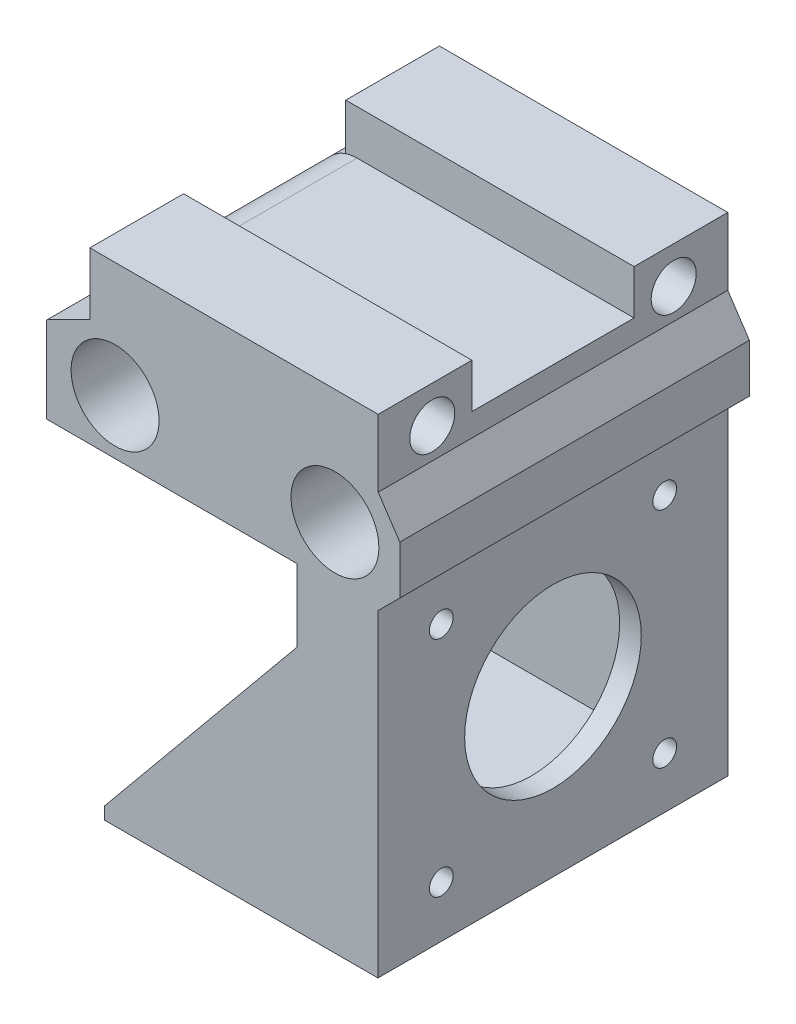
SolidWorks part; units mm, degrees
ref_plane "Front Plane" through (0, 0, 0) normal (0, 0, 1) x (1, 0, 0)
ref_plane "Top Plane" through (0, 0, 0) normal (0, 1, 0) x (1, 0, 0)
ref_plane "Right Plane" through (0, 0, 0) normal (1, 0, 0) x (0, 0, -1)
sketch "Sketch1" plane through (0, 0, 0) normal (0, 0, 1) x (1, 0, 0)
  line L0 (-37.9035, 31.8856) -> (4.5965, 31.8856)
  line L1 (-37.9035, 31.8856) -> (-37.9035, -23.9644)
  line L2 (-37.9035, -23.9644) -> (4.5965, -23.9644)
  line L3 (4.5965, -23.9644) -> (4.5965, 31.8856)
  dimension "D1" = 42.5
  dimension "D2" = 55.85
extrude "Boss-Extrude2" add sketch "Sketch1" along normal blind 42.5
sketch "Sketch5" plane through (0, 0, 42.5) normal (0, 0, 1) x (1, 0, 0)
  line L0 (-31.9035, 31.8856) -> (-31.9035, 20.046) construction
  line L1 (4.5965, 31.8856) -> (-37.9035, 31.8856) construction
  line L2 (-37.9035, 25.8856) -> (-26.7205, 25.8856) construction
  line L3 (-37.9035, 31.8856) -> (-37.9035, -23.9644) construction
  line L4 (-16.6535, 31.8856) -> (-16.6535, 20.4837) construction
  circle A0 centre (-31.9035, 25.9658) radius 3.175
  circle A1 centre (-1.4035, 25.9658) radius 3.175
  dimension "D3" = 6.35
  dimension "D1" = 6
  dimension "D2" = 6
extrude "Cut-Extrude2" cut sketch "Sketch5" against normal blind 42.5
sketch "Sketch6" plane through (-37.9035, 0, 0) normal (-1, 0, 0) x (0, 0, 1)
  line L0 (21.25, 22.7908) -> (21.25, -23.9644) construction
  line L1 (0, 22.7908) -> (42.5, 22.7908) construction
  line L2 (42.5, -23.9644) -> (0, -23.9644) construction
  line L3 (21.25, -0.5868) -> (0, -0.5868) construction
  line L4 (0, 31.8856) -> (0, -23.9644) construction
  line L5 (0, 20.6632) -> (42.5, 20.6632)
  line L6 (42.5, 31.8856) -> (42.5, -23.9644) construction
  line L7 (42.5, 20.6632) -> (42.5, -21.8368)
  line L8 (42.5, -21.8368) -> (0, -21.8368)
  line L9 (0, -21.8368) -> (0, 20.6632)
  dimension "D1" = 42.5
extrude "Cut-Extrude3" cut sketch "Sketch6" against normal blind 39.5
sketch "Sketch7" plane through (4.5965, 0, 0) normal (1, 0, 0) x (0, 0, -1)
  line L0 (-21.25, -21.8368) -> (-21.25, 20.6632) construction
  line L1 (0, -21.8368) -> (-42.5, -21.8368) construction
  line L2 (-42.5, 20.6632) -> (0, 20.6632) construction
  line L3 (-42.5, 20.6632) -> (0, 20.6632) construction
  line L4 (-42.5, -23.9644) -> (-42.5, 31.8856) construction
  line L5 (-42.5, -0.5868) -> (0, -0.5868) construction
  line L6 (0, 20.6632) -> (0, -21.8368) construction
  line L7 (0, -21.8368) -> (-42.5, -21.8368) construction
  line L8 (-42.5, -21.8368) -> (-42.5, 20.6632) construction
  line L9 (-42.5, -16.3368) -> (0, -16.3368) construction
  line L10 (-36.75, 20.6632) -> (-36.75, -21.8368) construction
  line L11 (-42.5, 14.6632) -> (0, 14.6632) construction
  circle A0 centre (-21.25, -0.5868) radius 12.25
  circle A1 centre (-36.75, -16.3368) radius 1.65
  circle A2 centre (-5.75, -16.3368) radius 1.65
  circle A3 centre (-36.75, 14.6632) radius 1.65
  circle A4 centre (-5.75, 14.6632) radius 1.65
  dimension "D1" = 5.5
  dimension "D3" = 31
  dimension "D5" = 31
  dimension "D6" = 3.3
  dimension "D7" = 3.3
  dimension "D8" = 24.5
  dimension "D2" = 31
  dimension "D4" = 6
extrude "Cut-Extrude4" cut sketch "Sketch7" against normal blind 39.5
sketch "Sketch9" plane through (0, -23.9644, 0) normal (0, -1, 0) x (1, 0, 0)
  line L0 (-37.9035, 42.5) -> (-27.9035, 42.5)
  line L1 (-37.9035, 42.5) -> (4.5965, 42.5) construction
  line L2 (-27.9035, 42.5) -> (-27.9035, 0)
  line L3 (-37.9035, 0) -> (4.5965, 0) construction
  line L4 (-27.9035, 0) -> (-37.9035, 0)
  line L5 (-37.9035, 0) -> (-37.9035, 42.5)
extrude "Cut-Extrude5" cut sketch "Sketch9" against normal blind 39.5
chamfer "Chamfer1" distance 3 angle 45 2 edges at (-37.9035, 31.8856, 21.25) (-37.9035, 20.6632, 21.25)
chamfer "Chamfer2" distance 2 angle 45 1 edges at (4.5965, -23.9644, 21.25)
sketch "Sketch10" plane through (-27.9035, 0, 0) normal (-1, 0, 0) x (0, 0, 1)
  line L1 (42.5, -23.9644) -> (45.5, -23.9644)
  line L4 (42.5, -21.8368) -> (45.5, -21.8368)
  line L5 (45.5, -21.8368) -> (45.5, -23.9644)
  line L7 (42.5, -21.8368) -> (42.5, -23.9644)
  line L8 (21.25, -21.8368) -> (21.25, -23.9644) construction
  line L9 (0, -21.8368) -> (42.5, -21.8368) construction
  line L10 (0, -23.9644) -> (42.5, -23.9644) construction
  line L11 (0, -21.8368) -> (-3, -21.8368)
  line L12 (-3, -21.8368) -> (-3, -23.9644)
  line L13 (0, -23.9644) -> (-3, -23.9644)
  line L14 (0, -21.8368) -> (0, -23.9644)
  dimension "D1" = 3
extrude "Boss-Extrude3" add sketch "Sketch10" against normal blind 3
sketch "Sketch12" plane through (1.5965, 0, 0) normal (-1, 0, 0) x (0, 0, 1)
  line L0 (42.5, 20.6632) -> (42.5, 17.6632)
  line L1 (42.5, -21.8368) -> (42.5, 20.6632) construction
  line L2 (42.5, 17.6632) -> (45.5, 17.6632)
  line L3 (45.5, 17.6632) -> (45.5, 20.6632)
  line L4 (45.5, 20.6632) -> (42.5, 20.6632)
  line L5 (21.25, 20.6632) -> (21.25, -21.8368) construction
  line L6 (42.5, 20.6632) -> (0, 20.6632) construction
  line L7 (-3, -21.8368) -> (45.5, -21.8368) construction
  line L8 (-3, 17.6632) -> (-3, 20.6632)
  line L9 (0, 17.6632) -> (-3, 17.6632)
  line L10 (0, 20.6632) -> (0, 17.6632)
  line L11 (-3, 20.6632) -> (0, 20.6632)
  dimension "D1" = 3
  dimension "D2" = 3
extrude "Boss-Extrude4" add sketch "Sketch12" against normal blind 3
sketch "Sketch13" plane through (0, 0, -3) normal (0, 0, -1) x (-1, 0, 0)
  line L0 (-1.5965, 17.6632) -> (24.9035, -21.8368)
  line L1 (-1.5965, 20.6632) -> (27.9035, -21.8368)
  line L2 (27.9035, -21.8368) -> (24.9035, -21.8368)
  line L3 (-1.5965, 20.6632) -> (-1.5965, 17.6632)
extrude "Boss-Extrude5" add sketch "Sketch13" against normal blind 2
sketch "Sketch14" plane through (0, 0, 45.5) normal (0, 0, 1) x (1, 0, 0)
  line L0 (1.5965, 17.6632) -> (-24.9035, -21.8368)
  line L1 (-24.9035, -21.8368) -> (-27.9035, -21.8368)
  line L2 (-27.9035, -21.8368) -> (1.5965, 20.6632)
  line L3 (1.5965, 20.6632) -> (1.5965, 17.6632)
extrude "Boss-Extrude6" add sketch "Sketch14" against normal blind 2
sketch "Sketch16" plane through (4.5965, 0, 0) normal (1, 0, 0) x (0, 0, -1)
  line L0 (-42.5, 30.0689) -> (-33.5, 30.0689)
  line L1 (-38, 42.2389) -> (-28.7582, 42.2389) construction
  line L2 (-42.5, 20.6632) -> (-42.5, 31.8856) construction
  line L3 (-33.5, 30.0689) -> (-33.5, 44.2389)
  line L4 (-33.5, 44.2389) -> (-42.5, 44.2389)
  line L5 (-42.5, 44.2389) -> (-42.5, 30.0689)
  line L6 (-21.25, 31.8856) -> (-21.25, 36.9569) construction
  line L7 (-42.5, 31.8856) -> (0, 31.8856) construction
  line L8 (-9, 44.2389) -> (0, 44.2389)
  line L9 (-9, 30.0689) -> (-9, 44.2389)
  line L10 (0, 30.0689) -> (-9, 30.0689)
  line L11 (0, 44.2389) -> (0, 30.0689)
  line L14 (-42.5, 39.1139) -> (-33.5, 39.1139) construction
  circle A0 centre (-38, 39.1139) radius 3.125
  circle A1 centre (-4.5, 39.1139) radius 3.125
  dimension "D3" = 6.25
  dimension "D4" = 2
  dimension "D1" = 9
  dimension "D2" = 14.17
extrude "Boss-Extrude8" add sketch "Sketch16" against normal blind 5
sketch "Sketch18" plane through (-0.4035, 0, 0) normal (-1, 0, 0) x (0, 0, 1)
  line L0 (0, 44.2389) -> (9, 44.2389)
  line L1 (9, 44.2389) -> (9, 31.8856)
  line L2 (9, 31.8856) -> (0, 31.8856)
  line L3 (0, 31.8856) -> (0, 44.2389)
  line L4 (21.25, 39.3131) -> (21.25, 31.8856) construction
  line L5 (0, 31.8856) -> (42.5, 31.8856) construction
  line L6 (33.5, 31.8856) -> (42.5, 31.8856)
  line L7 (33.5, 44.2389) -> (33.5, 31.8856)
  line L8 (42.5, 44.2389) -> (33.5, 44.2389)
  line L9 (42.5, 31.8856) -> (42.5, 44.2389)
extrude "Boss-Extrude9" add sketch "Sketch18" along normal blind 2
sketch "Sketch20" plane through (0, -23.9644, 0) normal (0, -1, 0) x (1, 0, 0)
  line L0 (-27.9035, 21.25) -> (2.5965, 21.25) construction
  line L1 (-27.9035, -3) -> (-27.9035, 45.5) construction
  line L2 (2.5965, 0) -> (2.5965, 42.5) construction
  line L3 (-12.6535, 21.25) -> (-12.159, 21.25)
  line L4 (-12.159, 21.25) -> (-12.159, 24.75)
  line L5 (-12.159, 24.75) -> (-12.6535, 24.75)
  line L6 (-12.6535, 24.75) -> (-12.6535, 21.25)
  dimension "D1" = 3.5
extrude "Boss-Extrude10" add sketch "Sketch20" along normal blind 0.2
sketch "Sketch22" plane through (0, 0, 42.5) normal (0, 0, 1) x (1, 0, 0)
  line L0 (-27.9035, -23.9644) -> (-27.9035, -24.9644)
  line L1 (-27.9035, -24.9644) -> (4.5965, -24.9644)
  line L2 (4.5965, -24.9644) -> (4.5965, -21.9644)
  line L3 (4.5965, -21.9644) -> (2.5965, -23.9644)
  line L4 (2.5965, -23.9644) -> (-27.9035, -23.9644)
extrude "Boss-Extrude11" add sketch "Sketch22" against normal blind 42.5
sketch "Sketch23" plane through (0, 0, 45.5) normal (0, 0, 1) x (1, 0, 0)
  line L0 (1.5965, -21.8368) -> (-33.4035, -21.8368)
  line L1 (-33.4035, -21.8368) -> (-33.4035, -24.8368)
  line L2 (-33.4035, -24.8368) -> (1.5965, -24.9644)
  line L3 (-27.9035, -24.9644) -> (4.5965, -24.9644) construction
  line L4 (1.5965, -24.9644) -> (1.5965, -21.8368)
  dimension "D1" = 35
extrude "Boss-Extrude12" add sketch "Sketch23" against normal blind 48.5
sketch "Sketch24" plane through (0, 0, 45.5) normal (0, 0, 1) x (1, 0, 0)
  line L0 (-27.9035, -24.8568) -> (-27.9035, -24.9644)
  line L1 (-27.9035, -24.9644) -> (1.5965, -24.9644)
  line L2 (1.5965, -24.9644) -> (-27.9035, -24.8568)
extrude "Cut-Extrude8" cut sketch "Sketch24" against normal blind 54.5
sketch "Sketch28" plane through (-0.091, -24.9582, 0) normal (-0.0036, -1, 0) x (1, -0.0036, 0)
  line L0 (-33.3127, 45.5) -> (-33.3127, -3)
  line L1 (-33.3127, -3) -> (1.6875, -3)
  line L3 (4.6875, 0) -> (4.6875, 42.5)
  line L5 (1.5321, 45.5) -> (-33.3127, 45.5)
  line L6 (1.5321, 45.5) -> (4.6875, 45.5)
  line L7 (4.6875, 45.5) -> (4.6875, 42.5)
  line L8 (1.6875, -3) -> (4.6875, -3)
  line L9 (4.6875, -3) -> (4.6875, 0)
extrude "Boss-Extrude15" add sketch "Sketch28" against normal blind 3
sketch "Sketch30" plane through (0, 0, 45.5) normal (0, 0, 1) x (1, 0, 0)
  line L0 (4.5965, 20.6632) -> (1.5965, 20.6632)
  line L1 (1.5965, 20.6632) -> (-33.4035, -21.8368)
  line L2 (-33.4035, -21.8368) -> (-33.4035, -24.8368)
  line L3 (-33.4035, -24.8368) -> (4.5965, -24.9753)
  line L4 (4.5965, -24.9753) -> (4.5965, 20.6632)
extrude "Boss-Extrude16" add sketch "Sketch30" against normal blind 3
sketch "Sketch31" plane through (4.5965, 0, 0) normal (1, 0, 0) x (0, 0, -1)
  line L0 (-45.5, 20.6632) -> (-40.5645, 20.6632)
  line L1 (-40.5645, 20.6632) -> (-40.5645, -21.9753)
  line L2 (0, -21.9753) -> (-42.5, -21.9753) construction
  line L3 (-40.5645, -21.9753) -> (-45.5, -21.8368)
  line L4 (-45.5, -21.8368) -> (-45.5, 20.6632)
extrude "Boss-Extrude17" add sketch "Sketch31" against normal blind 1
sketch "Sketch32" plane through (0, 0, -3) normal (0, 0, -1) x (-1, 0, 0)
  line L0 (-4.5965, 20.6632) -> (-4.5965, -24.9753)
  line L1 (-4.5965, -24.9753) -> (33.4035, -24.8368)
  line L3 (-1.5965, 20.6632) -> (-4.5965, 20.6632)
  line L4 (-1.5965, 20.6632) -> (33.4035, -21.8368)
  line L5 (33.4035, -21.8368) -> (33.4035, -24.8368)
extrude "Boss-Extrude19" add sketch "Sketch32" against normal blind 3
sketch "Sketch33" plane through (4.5965, 0, 0) normal (1, 0, 0) x (0, 0, -1)
  line L0 (3, 20.6632) -> (-2.5036, 20.6632)
  line L1 (-2.5036, 20.6632) -> (-2.5036, -21.9753)
  line L2 (3, -21.9753) -> (-45.5, -21.9753) construction
  line L3 (-2.5036, -21.9753) -> (3, -21.9753)
  line L4 (3, -21.9753) -> (3, 20.6632)
extrude "Boss-Extrude20" add sketch "Sketch33" against normal blind 1
sketch "Sketch34" plane through (0, 0, -3) normal (0, 0, -1) x (-1, 0, 0)
  line L0 (-4.5965, 20.6632) -> (34.9035, 20.6632)
  line L1 (-1.5965, 20.6632) -> (34.9035, 20.6632) construction
  line L2 (34.9035, 20.6632) -> (37.9035, 23.6632)
  line L3 (37.9035, 23.6632) -> (37.9035, 28.8856)
  line L4 (37.9035, 28.8856) -> (34.9035, 31.8856)
  line L5 (34.9035, 31.8856) -> (2.4035, 31.8856)
  line L6 (2.4035, 31.8856) -> (2.4035, 44.2389)
  line L7 (2.4035, 44.2389) -> (-4.5965, 44.2389)
  line L8 (-4.5965, 44.2389) -> (-4.5965, 20.6632)
  circle A0 centre (1.4035, 25.9658) radius 3.175
  circle A1 centre (31.9035, 25.9658) radius 3.175
extrude "Boss-Extrude21" add sketch "Sketch34" against normal blind 3
sketch "Sketch35" plane through (0, 0, 45.5) normal (0, 0, 1) x (1, 0, 0)
  line L0 (4.5965, 20.6632) -> (4.5965, 44.2389)
  line L1 (4.5965, 44.2389) -> (-2.4035, 44.2389)
  line L2 (-2.4035, 44.2389) -> (-2.4035, 31.8856)
  line L3 (-2.4035, 31.8856) -> (-34.9035, 31.8856)
  line L4 (-34.9035, 31.8856) -> (-37.9035, 28.8856)
  line L5 (-37.9035, 28.8856) -> (-37.9035, 23.6632)
  line L6 (4.5965, 20.6632) -> (-34.9035, 20.6632)
  line L7 (-37.9035, 23.6632) -> (-34.9035, 20.6632)
  circle A0 centre (-31.9035, 25.9658) radius 3.175
  circle A1 centre (-1.4035, 25.9658) radius 3.175
extrude "Boss-Extrude22" add sketch "Sketch35" against normal blind 3
sketch "Sketch36" plane through (0, 0, -3) normal (0, 0, -1) x (-1, 0, 0)
  line L0 (-1.5965, 20.6632) -> (6.6388, 10.6632)
  line L1 (33.4035, -21.8368) -> (-1.5965, 20.6632) construction
  line L2 (6.6388, 10.6632) -> (6.6388, 20.6632)
  line L3 (-1.5965, 20.6632) -> (34.9035, 20.6632) construction
  line L4 (6.6388, 20.6632) -> (-1.5965, 20.6632)
  dimension "D1" = 10
extrude "Boss-Extrude23" add sketch "Sketch36" against normal blind 3
sketch "Sketch37" plane through (0, 0, 45.5) normal (0, 0, 1) x (1, 0, 0)
  line L0 (-6.6388, 20.6632) -> (-6.6388, 10.6632)
  line L1 (-6.6388, 10.6632) -> (1.5965, 20.6632)
  line L2 (1.5965, 20.6632) -> (-6.6388, 20.6632)
extrude "Boss-Extrude24" add sketch "Sketch37" against normal blind 3
sketch "Sketch40" plane through (4.6874, -0.0171, 0) normal (1, -0.0036, 0) x (0, 0, -1)
  line L0 (-45.5, -21.8199) -> (-45.5, -24.9584)
  line L1 (-45.5, -24.9584) -> (3, -24.9584)
  line L2 (3, -24.9584) -> (3, -21.9584)
  line L3 (3, -21.9584) -> (-45.5, -21.8199)
extrude "Cut-Extrude10" cut sketch "Sketch40" against normal blind 1
sketch "Sketch41" plane through (4.5965, 0, 0) normal (1, 0, 0) x (0, 0, -1)
  line L0 (-45.5, -20.2014) -> (-45.5, -24.9716)
  line L1 (-45.5, -21.8368) -> (-45.5, 44.2389) construction
  line L2 (-45.5, -24.9716) -> (3, -24.9716)
  line L3 (3, -24.9716) -> (3, -20.2014)
  line L4 (3, 44.2389) -> (3, -21.9753) construction
  line L5 (3, -20.2014) -> (-45.5, -20.2014)
extrude "Boss-Extrude25" add sketch "Sketch41" against normal blind 1.3
chamfer "Chamfer3" distance 1.5 angle 45 2 edges at (4.5965, -24.9716, 21.25) (3.2965, -24.9716, 21.25)
sketch "Sketch44" plane through (4.5965, 0, 0) normal (1, 0, 0) x (0, 0, -1)
  line L0 (-33.5, 44.2389) -> (-33.5, 31.8856)
  line L1 (-33.5, 31.8856) -> (-32.5, 31.8856)
  line L2 (-33.5, 31.8856) -> (-9, 31.8856) construction
  line L3 (-33.5, 44.2389) -> (-32.5, 44.2389)
  line L4 (-32.5, 44.2389) -> (-32.5, 31.8856)
  line L5 (-21.25, 31.8856) -> (-21.25, 40.2345) construction
  line L6 (-9, 44.2389) -> (-10, 44.2389)
  line L7 (-9, 44.2389) -> (-9, 31.8856)
  line L8 (-9, 31.8856) -> (-10, 31.8856)
  line L9 (-10, 44.2389) -> (-10, 31.8856)
extrude "Boss-Extrude26" add sketch "Sketch44" against normal blind 7
sketch "Sketch45" plane through (4.5965, 0, 0) normal (1, 0, 0) x (0, 0, -1)
  line L0 (-45.5, 44.2389) -> (-45.5, 35.7389)
  line L1 (-45.5, -23.4716) -> (-45.5, 44.2389) construction
  line L2 (-45.5, 35.7389) -> (-32.5, 35.7389)
  line L3 (-32.5, 35.7389) -> (-32.5, 44.2389)
  line L4 (-32.5, 44.2389) -> (-45.5, 44.2389)
  line L5 (-10, 44.2389) -> (3, 44.2389)
  line L6 (3, 44.2389) -> (3, 30.5689)
  line L7 (3, 44.2389) -> (3, -23.4716) construction
  line L8 (3, 30.5689) -> (-10, 30.5689)
  line L9 (-10, 30.5689) -> (-10, 44.2389)
  circle A0 centre (-38, 39.1139) radius 3.125
  circle A1 centre (-4.5, 39.1139) radius 3.125
  dimension "D2" = 6.25
  dimension "D3" = 6.25
  dimension "D1" = 8.5
extrude "Boss-Extrude27" add sketch "Sketch45" against normal blind 40
sketch "Sketch46" plane through (4.5965, 0, 0) normal (1, 0, 0) x (0, 0, -1)
  circle A0 centre (-38, 39.1139) radius 3.125
  circle A1 centre (-4.5, 39.1139) radius 3.125
  dimension "D1" = 6.25
  dimension "D2" = 6.25
extrude "Cut-Extrude11" cut sketch "Sketch46" against normal blind 49
sketch "Sketch47" plane through (-33.4035, 0, 0) normal (-1, 0, 0) x (0, 0, 1)
  line L0 (-3, -24.9033) -> (-3, -23.9033)
  line L1 (-3, -24.8368) -> (-3, -24.9698) construction
  line L2 (-3, -23.9033) -> (45.5, -23.9033)
  line L3 (45.5, -21.8368) -> (45.5, -24.8368) construction
  line L4 (45.5, -23.9033) -> (45.5, -24.8368)
  line L5 (45.5, -24.8368) -> (-3, -24.9033)
  dimension "D1" = 1
extrude "Cut-Extrude12" cut sketch "Sketch47" against normal blind 68
sketch "Sketch48" plane through (-33.4035, 0, 0) normal (-1, 0, 0) x (0, 0, 1)
  line L0 (-2.9298, -24.1855) -> (-2.9298, -25.5194)
  line L1 (-2.9298, -25.5194) -> (45.7589, -25.7862)
  line L2 (45.7589, -25.7862) -> (45.7589, -24.1855)
  line L3 (45.7589, -24.1855) -> (-2.9298, -24.1855)
extrude "Cut-Extrude13" cut sketch "Sketch48" against normal blind 68
sketch "Sketch49" plane through (-33.4035, 0, 0) normal (-1, 0, 0) x (0, 0, 1)
  line L0 (-3.479, -24.095) -> (-0.835, -24.095)
  line L1 (-0.835, -24.095) -> (-0.835, -25.2614)
  line L2 (-0.835, -25.2614) -> (-3.479, -25.2614)
  line L3 (-3.479, -25.2614) -> (-3.479, -24.095)
extrude "Cut-Extrude14" cut sketch "Sketch49" against normal blind 68
sketch "Sketch51" plane through (0, 0, 45.5) normal (0, 0, 1) x (1, 0, 0)
  line L0 (-35.4035, 35.7389) -> (-35.4035, 31.3856)
  line L1 (-35.4035, 31.3856) -> (-34.9035, 31.8856)
  line L2 (-34.9035, 31.8856) -> (-2.4035, 31.8856)
  line L3 (-2.4035, 31.8856) -> (-2.4035, 35.7389)
  line L4 (-2.4035, 35.7389) -> (-35.4035, 35.7389)
extrude "Boss-Extrude28" add sketch "Sketch51" against normal blind 13
sketch "Sketch52" plane through (0, 0, 45.5) normal (0, 0, 1) x (1, 0, 0)
  line L2 (-41.4035, 20.6632) -> (-34.9035, 20.6632)
  line L3 (-34.9035, 20.6632) -> (-37.9035, 23.6632)
  line L4 (-37.9035, 23.6632) -> (-37.9035, 28.8856)
  line L5 (-37.9035, 28.8856) -> (-35.4035, 31.3856)
  line L6 (-35.4035, 31.3856) -> (-35.4035, 32.6405)
  line L7 (-35.4035, 44.2389) -> (-35.4035, 31.3856) construction
  line L8 (-35.4035, 32.6405) -> (-41.4035, 32.6405)
  line L10 (-41.4035, 32.6405) -> (-41.4035, 20.6632)
extrude "Boss-Extrude29" add sketch "Sketch52" against normal blind 48.5
sketch "Sketch53" plane through (0, 0, 45.5) normal (0, 0, 1) x (1, 0, 0)
  line L0 (4.5965, 31.8856) -> (6.5965, 31.8856)
  line L1 (6.5965, 31.8856) -> (6.5965, 20.6632)
  line L2 (6.5965, 20.6632) -> (4.5965, 20.6632)
  line L3 (4.5965, -23.4716) -> (4.5965, 44.2389) construction
  line L4 (4.5965, 20.6632) -> (4.5965, 31.8856)
extrude "Boss-Extrude30" add sketch "Sketch53" against normal blind 48.5
chamfer "Chamfer4" distance 2 angle 45 2 edges at (6.5965, 20.6632, 21.25) (6.5965, 31.8856, 21.25)
sketch "Sketch55" plane through (0, 0, 45.5) normal (0, 0, 1) x (1, 0, 0)
  line L0 (-41.4035, 25.9658) -> (6.5965, 25.9658) construction
  line L1 (-41.4035, 32.6405) -> (-41.4035, 20.6632) construction
  line L2 (6.5965, 22.6632) -> (6.5965, 29.8856) construction
  line L3 (-31.9035, 18.9211) -> (-31.9035, 33.3719) construction
  line L4 (-1.4035, 18.9211) -> (-1.4035, 34.1612) construction
  line L5 (-41.4035, 27.3658) -> (6.5965, 27.3658) construction
  line L6 (-31.9035, 22.1632) -> (-49.8479, 22.1632) construction
  line L7 (-41.4035, 20.6632) -> (-49.8479, 20.6632) construction
  line L8 (-31.9035, 22.1632) -> (-1.3903, 22.1632) construction
  line L9 (-41.4035, 28.2632) -> (6.5965, 28.2632) construction
  circle A0 centre (-31.9035, 28.2632) radius 6.1
  circle A1 centre (-1.4035, 28.2632) radius 6.1
  dimension "D1" = 1.4
  dimension "D3" = 12.2
  dimension "D4" = 12.2
  dimension "D2" = 1.5
sketch "Sketch57" plane through (4.5965, 0, 0) normal (1, 0, 0) x (0, 0, -1)
  line L1 (-32.5, 31.8856) -> (-32.5, 44.2389) construction
  line L4 (-10, 31.8856) -> (-10, 38.0623)
  line L5 (-10, 44.2389) -> (-10, 31.8856) construction
  line L6 (-10, 38.0623) -> (-32.5, 38.0623)
  line L7 (-32.5, 38.0623) -> (-32.5, 31.8856)
  line L8 (-32.5, 31.8856) -> (-10, 31.8856)
extrude "Boss-Extrude32" add sketch "Sketch57" against normal blind 46
sketch "Sketch58" plane through (0, 0, 45.5) normal (0, 0, 1) x (1, 0, 0)
  line L0 (4.5965, 31.8856) -> (6.5965, 29.8856)
  line L1 (6.5965, 29.8856) -> (6.5965, 31.8856)
  line L2 (6.5965, 31.8856) -> (4.5965, 31.8856)
extrude "Boss-Extrude33" add sketch "Sketch58" against normal blind 48.5
sketch "Sketch60" plane through (0, 0, 45.5) normal (0, 0, 1) x (1, 0, 0)
  line L0 (-35.4035, 35.6405) -> (-41.4035, 32.6405)
  line L1 (-35.4035, 44.2389) -> (-35.4035, 32.6405) construction
  line L2 (-41.4035, 32.6405) -> (-35.4035, 32.6405)
  line L3 (-35.4035, 32.6405) -> (-35.4035, 35.6405)
  dimension "D1" = 3
extrude "Boss-Extrude35" add sketch "Sketch60" against normal blind 48.5
extrude "Cut-Extrude15" cut sketch "Sketch55" against normal blind 48.5
sketch "Sketch61" plane through (0, 0, 45.5) normal (0, 0, 1) x (1, 0, 0)
  line L0 (4.5965, 31.8856) -> (6.5965, 31.8856)
  line L1 (6.5965, 31.8856) -> (4.5965, 34.8856)
  line L2 (4.5965, 31.8856) -> (4.5965, 44.2389) construction
  line L3 (4.5965, 34.8856) -> (4.5965, 31.8856)
  dimension "D1" = 3
extrude "Boss-Extrude36" add sketch "Sketch61" against normal blind 48.5
sketch "Sketch62" plane through (-33.4035, 0, 0) normal (-1, 0, 0) x (0, 0, 1)
  line L0 (-3, -23.9033) -> (-3, -23.5033)
  line L2 (-3, -21.8368) -> (-3, -23.9033) construction
  line L3 (-3, -23.9033) -> (45.5, -23.9033)
  line L4 (45.5, -23.9033) -> (45.5, -23.5033)
  line L5 (45.5, -23.5033) -> (-3, -23.5033)
extrude "Cut-Extrude16" cut sketch "Sketch62" against normal blind 48.5
chamfer "Chamfer5" distance 5.5 angle 45 1 edges at (-41.4035, 38.0623, 21.25)
fillet "Fillet1" radius 5 1 edges at (-35.9035, 38.0623, 21.25)
sketch "Sketch65" plane through (0, -23.5033, 0) normal (0, -1, 0) x (1, 0, 0)
  line L0 (-14.4193, 45.5) -> (-14.4193, -3) construction
  line L1 (4.5649, 45.5) -> (-33.4035, 45.5) construction
  line L2 (4.5649, -3) -> (-33.4035, -3) construction
  line L3 (-33.4035, 21.25) -> (4.5965, 21.25) construction
  line L4 (-33.4035, 45.5) -> (-33.4035, -3) construction
  line L5 (4.5965, -3) -> (4.5965, 45.5) construction
  line L6 (-14.4193, 16.25) -> (-18.9193, 16.25)
  line L7 (-18.9193, 16.25) -> (-18.9193, 26.25)
  line L8 (-18.9193, 26.25) -> (-9.9193, 26.25)
  line L9 (-9.9193, 26.25) -> (-9.9193, 16.25)
  line L10 (-9.9193, 16.25) -> (-14.4193, 16.25)
  dimension "D1" = 10
  dimension "D2" = 9
extrude "Cut-Extrude17" cut sketch "Sketch65" against normal blind 1
sketch "Sketch67" plane through (0, 0, 45.5) normal (0, 0, 1) x (1, 0, 0)
  line L0 (-1.4035, 28.2632) -> (19.3564, 28.2632) construction
  line L1 (4.5965, 42.2389) -> (4.5965, 35.9889) construction
  line L2 (4.5965, 39.1139) -> (19.3564, 39.1139) construction
  line L3 (4.5965, 11.6632) -> (4.5965, -12.8368) construction
  line L4 (4.5965, -0.5868) -> (19.3564, -0.5868) construction
  line L5 (-34.159, 33.9309) -> (-47.869, 27.0759) construction
  line L6 (-35.4035, 35.6405) -> (-41.2471, 32.7187) construction
  line L7 (6.5965, 31.8856) -> (7.5965, 30.3856)
  line L9 (7.5965, 30.3856) -> (7.5965, 23.6632)
  line L10 (7.5965, 23.6632) -> (6.5965, 22.6632)
  line L11 (6.5965, 22.6632) -> (6.5965, 31.8856)
  line L12 (4.5965, 20.6632) -> (6.5965, 22.6632) construction
  line L13 (6.5965, 31.8856) -> (4.5965, 34.8856) construction
  circle A0 centre (-31.9035, 28.2632) radius 6.1 construction
  dimension "D1" = 10.8507
  dimension "D2" = 39.7007
  dimension "D3" = 28.85
  dimension "D4" = 1
extrude "Boss-Extrude37" add sketch "Sketch67" against normal blind 48.5
